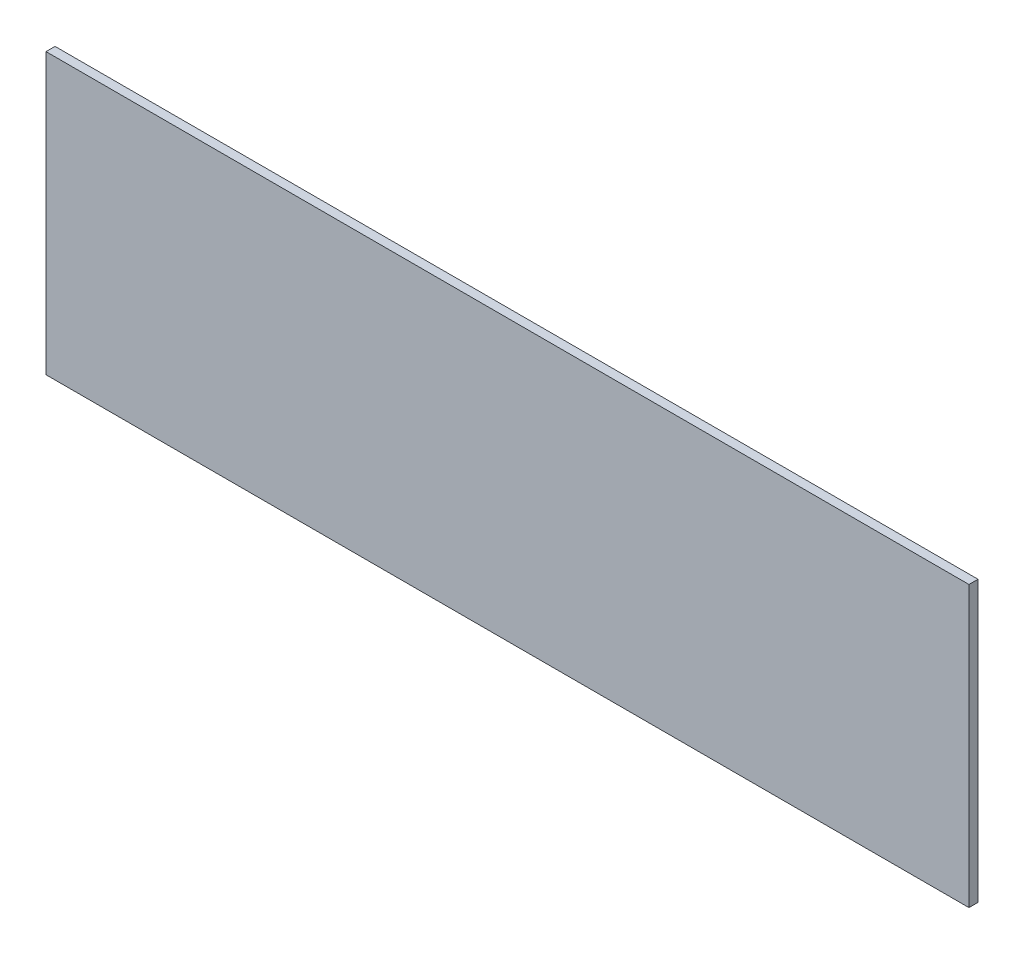
SolidWorks part; units mm, degrees
ref_plane "Front Plane" through (0, 0, 0) normal (0, 0, 1) x (1, 0, 0)
ref_plane "Top Plane" through (0, 0, 0) normal (0, 1, 0) x (1, 0, 0)
ref_plane "Right Plane" through (0, 0, 0) normal (1, 0, 0) x (0, 0, -1)
sketch "Sketch1" plane through (0, 0, 0) normal (0, 0, 1) x (1, 0, 0)
  line L1 (0, 0) -> (155, 0)
  line L2 (0, 0) -> (0, 47)
  line L3 (0, 47) -> (155, 47)
  line L4 (155, 0) -> (155, 47)
  dimension "D1" = 155
  dimension "D2" = 47
extrude "Boss-Extrude1" add sketch "Sketch1" along normal blind 1.5189
